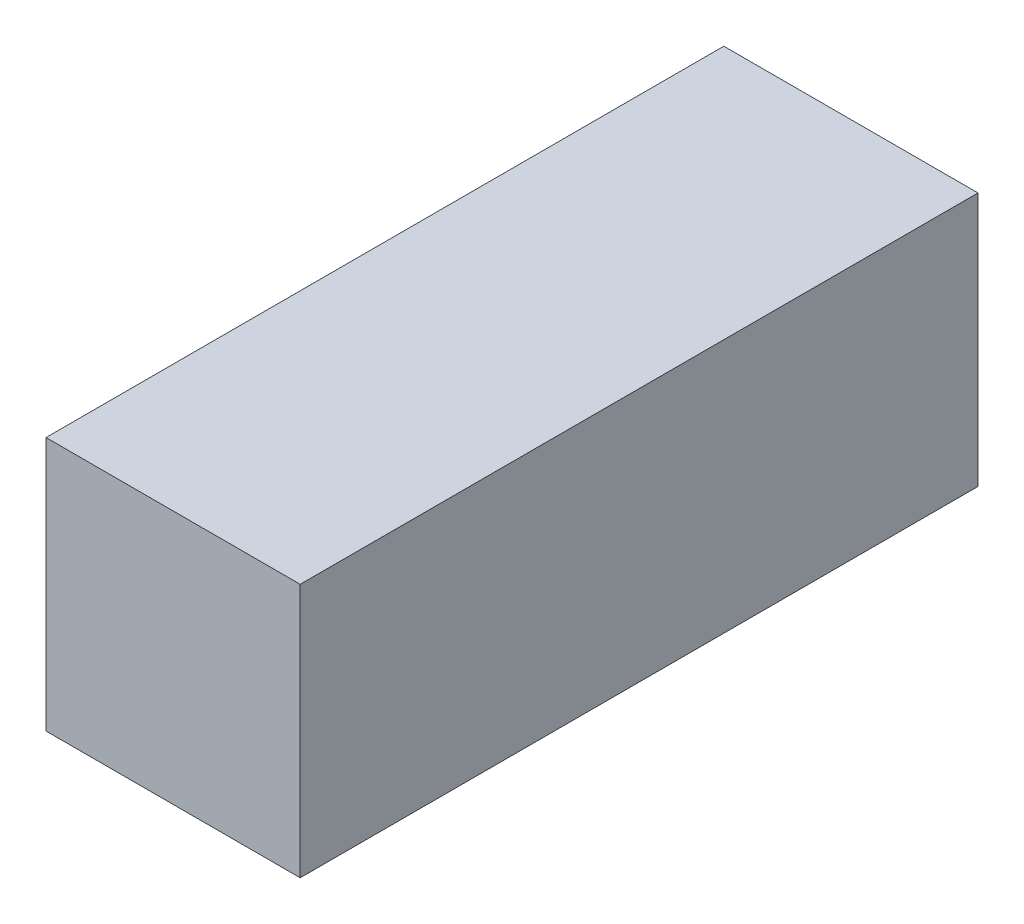
SolidWorks part; units mm, degrees
material "Pine"
ref_plane "Front Plane" through (0, 0, 0) normal (0, 0, 1) x (1, 0, 0)
ref_plane "Top Plane" through (0, 0, 0) normal (0, 1, 0) x (1, 0, 0)
ref_plane "Right Plane" through (0, 0, 0) normal (1, 0, 0) x (0, 0, -1)
sketch "Sketch1" plane through (0, 0, 0) normal (0, 0, 1) x (1, 0, 0)
  line L1 (-8.7312, 31.8492) -> (29.3688, 31.8492)
  line L2 (-8.7312, 31.8492) -> (-8.7312, -6.2508)
  line L3 (-8.7312, -6.2508) -> (29.3688, -6.2508)
  line L4 (29.3688, 31.8492) -> (29.3688, -6.2508)
  dimension "D1" = 38.1
  dimension "D2" = 38.1
extrude "Boss-Extrude1" add sketch "Sketch1" along normal blind 101.6
